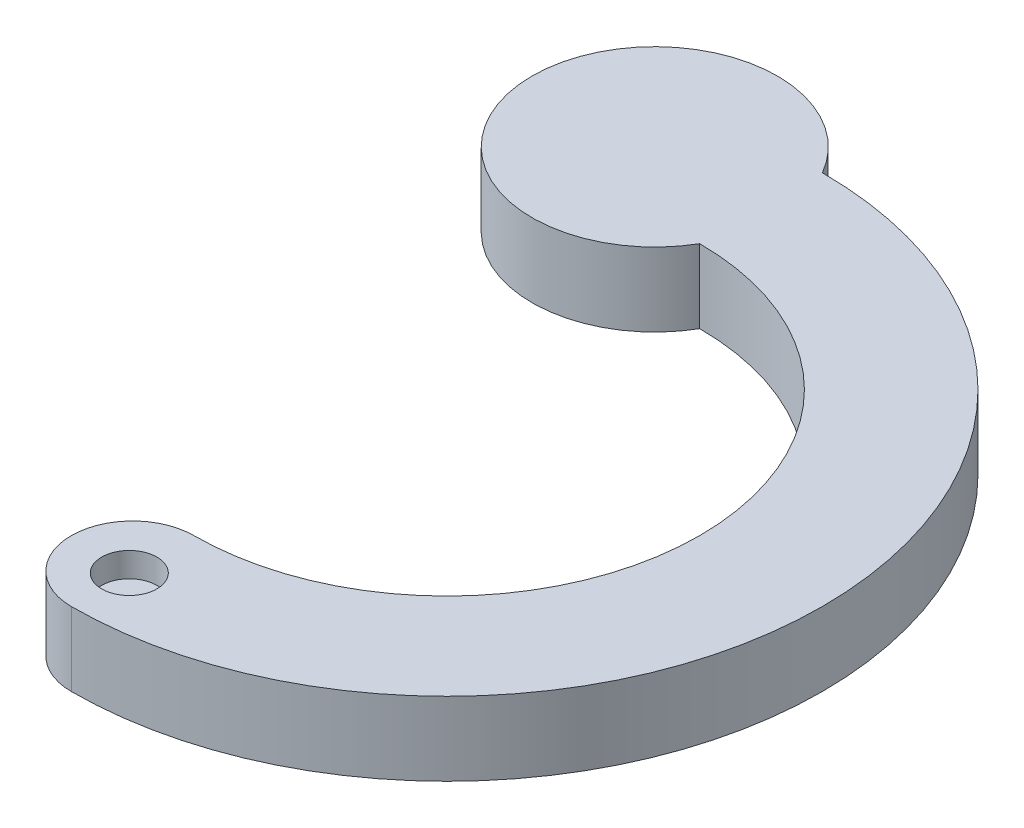
SolidWorks part; units mm, degrees
ref_plane "Front Plane" through (0, 0, 0) normal (0, 0, 1) x (1, 0, 0)
ref_plane "Top Plane" through (0, 0, 0) normal (0, 1, 0) x (1, 0, 0)
ref_plane "Right Plane" through (0, 0, 0) normal (1, 0, 0) x (0, 0, -1)
sketch "Sketch1" plane through (0, 0, 0) normal (0, 1, 0) x (1, 0, 0)
  line L0 (0, 0) -> (0, 51.2) construction
  line L3 (0, 61.2) -> (0, 79.6265) construction
  arc A0 (0, 0) -> (0, 61.2) centre (0, 30.6) ccw
  arc A1 (0, 10) -> (0, 51.2) centre (0, 30.6) ccw
  arc A2 (0, 61.2) -> (0, 51.2) centre (-8.6603, 56.2) ccw
  arc A3 (0, 10) -> (0, 0) centre (0, 5) ccw
  dimension "D1" = 20.6
  dimension "D2" = 30.6
  dimension "D5" = 20
  dimension "D3" = 10
  dimension "D4" = 10
extrude "Boss-Extrude1" add sketch "Sketch1" along normal mid plane 6
sketch "Sketch2" plane through (0, 3, 0) normal (0, 1, 0) x (1, 0, 0)
  circle A0 centre (0, 4.7275) radius 2.25
  dimension "D1" = 4.5
extrude "Cut-Extrude1" cut sketch "Sketch2" against normal blind 2
